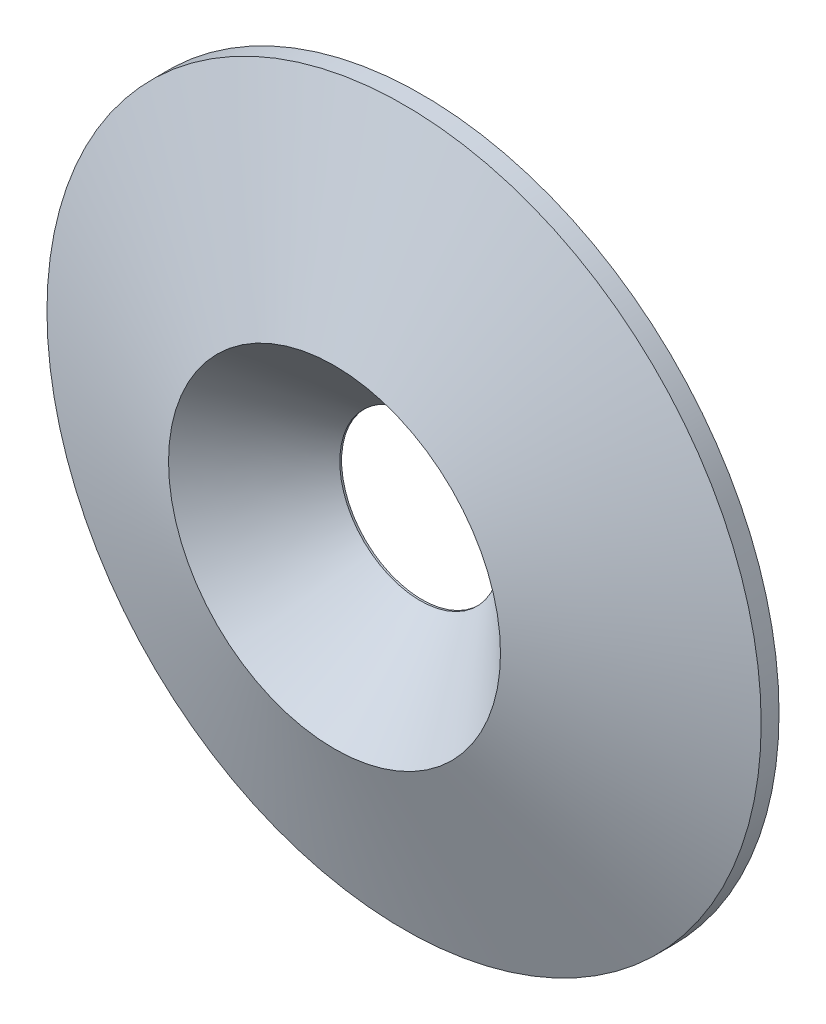
SolidWorks part; units mm, degrees
ref_plane "Front Plane" through (0, 0, 0) normal (0, 0, 1) x (1, 0, 0)
ref_plane "Top Plane" through (0, 0, 0) normal (0, 1, 0) x (1, 0, 0)
ref_plane "Right Plane" through (0, 0, 0) normal (1, 0, 0) x (0, 0, -1)
sketch "Sketch1" plane through (0, 0, 0) normal (0, 0, 1) x (1, 0, 0)
  circle A0 centre (0, 0) radius 10
  dimension "D1" = 20
extrude "Boss-Extrude1" add sketch "Sketch1" along normal blind 2.5
hole_wizard "CSK for M4 Flat Head Machine Screw1" positions "Sketch2" profile "Sketch3" countersink size "M4" standard "ANSI Metric" end condition through all
sketch "Sketch2" plane through (0, 0, 2.5) normal (0, 0, 1) x (1, 0, 0)
  point P0 (0, 0)
sketch "Sketch3" plane through (0, 0, 2.5) normal (1, 0, 0) x (0, -1, 0)
  line L0 (0, 0) -> (0, 2.5)
  line L1 (0, 2.5) -> (2.25, 2.5)
  line L2 (2.25, 2.5) -> (2.25, 2.45)
  line L3 (2.25, 2.45) -> (4.7, 0)
  line L5 (4.7, 0) -> (0, 0)
  line L6 (-2.25, 2.45) -> (-4.7, 0) construction
  line L11 (0, -6.35) -> (0, 107.95) construction
  dimension "Thru Hole Dia." = 4.5
  dimension "Thru Hole Depth" = 2.5
  dimension "Near C'Sink Dia." = 9.4
  dimension "Near C'Sink Angle" = 90
chamfer "Chamfer1" distance 2 angle 70 1 edges at (10, 0, 2.5) first distance on face at (10, 0, 2.5)
